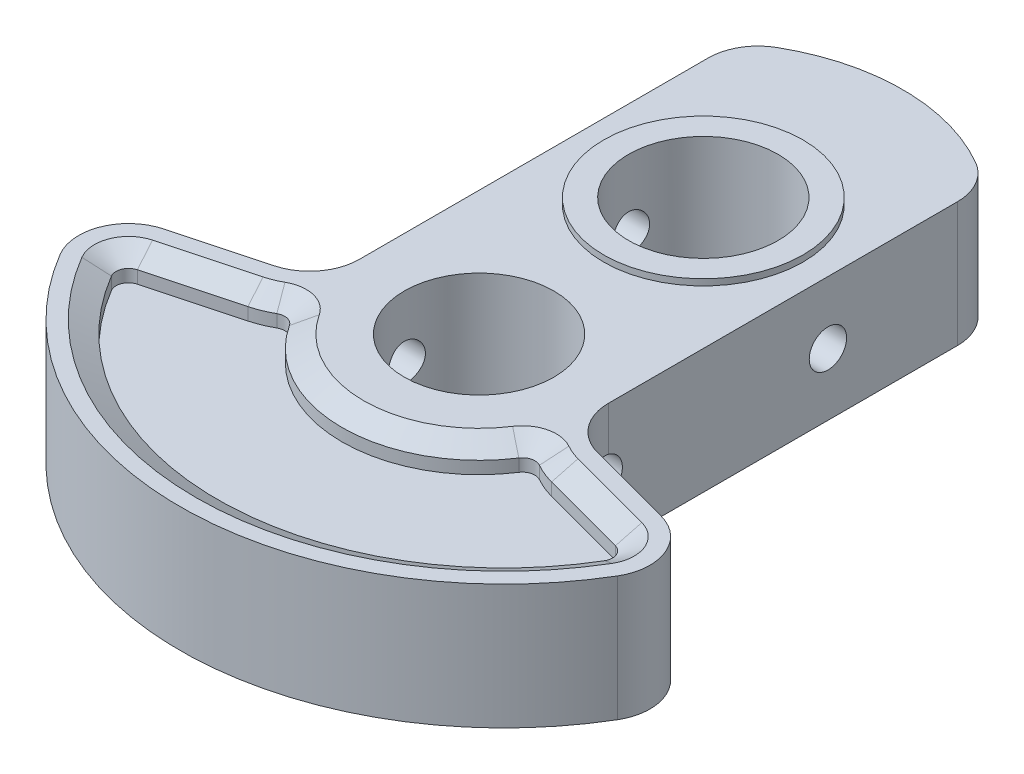
SolidWorks part; units mm, degrees
ref_plane "Front Plane" through (0, 0, 0) normal (0, 0, 1) x (1, 0, 0)
ref_plane "Top Plane" through (0, 0, 0) normal (0, 1, 0) x (1, 0, 0)
ref_plane "Right Plane" through (0, 0, 0) normal (1, 0, 0) x (0, 0, -1)
sketch "Sketch1" plane through (0, 0, 0) normal (0, 1, 0) x (1, 0, 0)
  line L0 (0, 48.0841) -> (0, -26.2277) construction
  line L1 (-10, 30.49) -> (-10, -2.6795)
  line L2 (10, 30.49) -> (10, -2.6795)
  line L3 (-10, 48.0841) -> (-10, -26.2277) construction
  line L4 (10, 48.0841) -> (10, -26.2277) construction
  line L5 (0, 0) -> (-24.5447, -6.5767) construction
  line L6 (0, 0) -> (24.5447, -6.5767) construction
  line L7 (-10, -2.6795) -> (-24.5447, -6.5767)
  line L8 (10, -2.6795) -> (24.5447, -6.5767)
  arc A1 (10, 30.49) -> (-10, 30.49) centre (0, 18) ccw
  arc A2 (-24.5447, -6.5767) -> (24.5447, -6.5767) centre (0, 2) ccw
  dimension "D5" = 26
  dimension "D2" = 18
  dimension "D3" = 10
  dimension "D6" = 75
  dimension "D7" = 75
  dimension "D4" = 10
extrude "Boss-Extrude1" add sketch "Sketch1" along normal mid plane 10
fillet "Fillet1" radius 4 6 edges at (24.5447, 0, 6.5767) (10, 0, 2.6795) (-24.5447, 0, 6.5767) (-10, 0, 2.6795) (-10, 0, -30.49) (10, 0, -30.49)
sketch "Sketch3" plane through (0, -5, 0) normal (0, -1, 0) x (1, 0, 0)
  circle A0 centre (0, 0) radius 8
  dimension "D1" = 16
extrude "Boss-Extrude2" add sketch "Sketch3" along normal mid plane 1
sketch "Sketch4" plane through (0, 5, 0) normal (0, 1, 0) x (1, 0, 0)
  circle A0 centre (0, 18) radius 8
  dimension "D1" = 16
  dimension "D2" = 18
extrude "Boss-Extrude3" add sketch "Sketch4" along normal mid plane 1
sketch "Sketch5" plane through (0, -5.5, 0) normal (0, -1, 0) x (1, 0, 0)
  circle A0 centre (0, 0) radius 6
  circle A2 centre (0, -18) radius 6
  dimension "D1" = 12
  dimension "D2" = 12
extrude "Cut-Extrude3" cut sketch "Sketch5" against normal through all
sketch "Sketch6" plane through (0, 5, 0) normal (0, 1, 0) x (1, 0, 0)
  line L11 (12.1883, -6.3717) -> (19.1869, -8.2469)
  line L12 (-19.1869, -8.2469) -> (-12.1883, -6.3717)
  line L13 (12.1883, -6.3717) -> (19.1869, -8.2469)
  line L14 (-19.1869, -8.2469) -> (-12.1883, -6.3717)
  arc A20 (-9.2082, -6.0173) -> (9.2082, -6.0173) centre (0, 0) ccw
  arc A21 (9.2082, -6.0173) -> (10.5397, -5.6951) centre (10.0453, -6.5644) cw
  arc A22 (-9.2082, -6.0173) -> (-10.5397, -5.6951) centre (-10.0453, -6.5644) ccw
  arc A25 (7, 0.3898) -> (12.1883, -6.3717) centre (14, 0.3898) ccw
  arc A26 (-12.1883, -6.3717) -> (-7, 0.3898) centre (-14, 0.3898) ccw
  arc A27 (19.7884, -9.7225) -> (19.1869, -8.2469) centre (18.9281, -9.2129) ccw
  arc A28 (-19.1869, -8.2469) -> (-19.7884, -9.7225) centre (-18.9281, -9.2129) ccw
  arc A29 (-19.7884, -9.7225) -> (19.7884, -9.7225) centre (0, 2) ccw
  arc A30 (10.5397, -5.6951) -> (12.1883, -6.3717) centre (14, 0.3898) ccw
  arc A31 (-12.1883, -6.3717) -> (-10.5397, -5.6951) centre (-14, 0.3898) ccw
  arc A32 (19.7884, -9.7225) -> (19.1869, -8.2469) centre (18.9281, -9.2129) ccw
  arc A33 (-19.1869, -8.2469) -> (-19.7884, -9.7225) centre (-18.9281, -9.2129) ccw
  arc A34 (-19.7884, -9.7225) -> (19.7884, -9.7225) centre (0, 2) ccw
  dimension "D2" = 22
  dimension "D3" = 1
  dimension "D1" = 3
extrude "Cut-Extrude4" cut sketch "Sketch6" against normal blind 2
chamfer "Chamfer1" distance 1 angle 60 10 edges at (11.3424, 5, 6.0861) (9.8101, 5, 5.5924) (15.6876, 5, 7.3093) (0, 5, 11) (19.8541, 5, 8.8354) (-9.8101, 5, 5.5924) (0, 5, 21) (-11.3424, 5, 6.0861) (-19.8541, 5, 8.8354) (-15.6876, 5, 7.3093) first distance on face at (11.3532, 4, 6.0597) first distance on face at (9.842, 4, 5.7243) first distance on face at (15.6876, 4, 7.3093) first distance on face at (0, 4, 8.5087) first distance on face at (19.6709, 4, 8.9101) first distance on face at (-9.842, 4, 5.7243) first distance on face at (0, 4, 15.3613) first distance on face at (-11.3532, 4, 6.0597) first distance on face at (-19.6709, 4, 8.9101) first distance on face at (-15.6876, 4, 7.3093)
mirror "Mirror5" about plane through (0, 0, 0) normal (0, 1, 0) of "Cut-Extrude4"
chamfer "Chamfer2" distance 1 angle 60 10 edges at (-11.3424, -5, 6.0861) (-15.6876, -5, 7.3093) (-9.8101, -5, 5.5924) (-19.8541, -5, 8.8354) (0, -5, 11) (0, -5, 21) (9.8101, -5, 5.5924) (19.8541, -5, 8.8354) (11.3424, -5, 6.0861) (15.6876, -5, 7.3093) first distance on face at (-11.3532, -4, 6.0597) first distance on face at (-15.6876, -4, 7.3093) first distance on face at (-9.842, -4, 5.7243) first distance on face at (-19.6709, -4, 8.9101) first distance on face at (0, -4, 8.5087) first distance on face at (0, -4, 15.3613) first distance on face at (9.842, -4, 5.7243) first distance on face at (19.6709, -4, 8.9101) first distance on face at (11.3532, -4, 6.0597) first distance on face at (15.6876, -4, 7.3093)
sketch "Sketch7" plane through (0, 0, 0) normal (1, 0, 0) x (0, 0, -1)
  circle A0 centre (0, 0) radius 1.5
  circle A1 centre (18, 0) radius 1.5
  dimension "D1" = 3
  dimension "D2" = 3
  dimension "D3" = 18
extrude "Cut-Extrude5" cut sketch "Sketch7" against normal through all both and the other way through all
